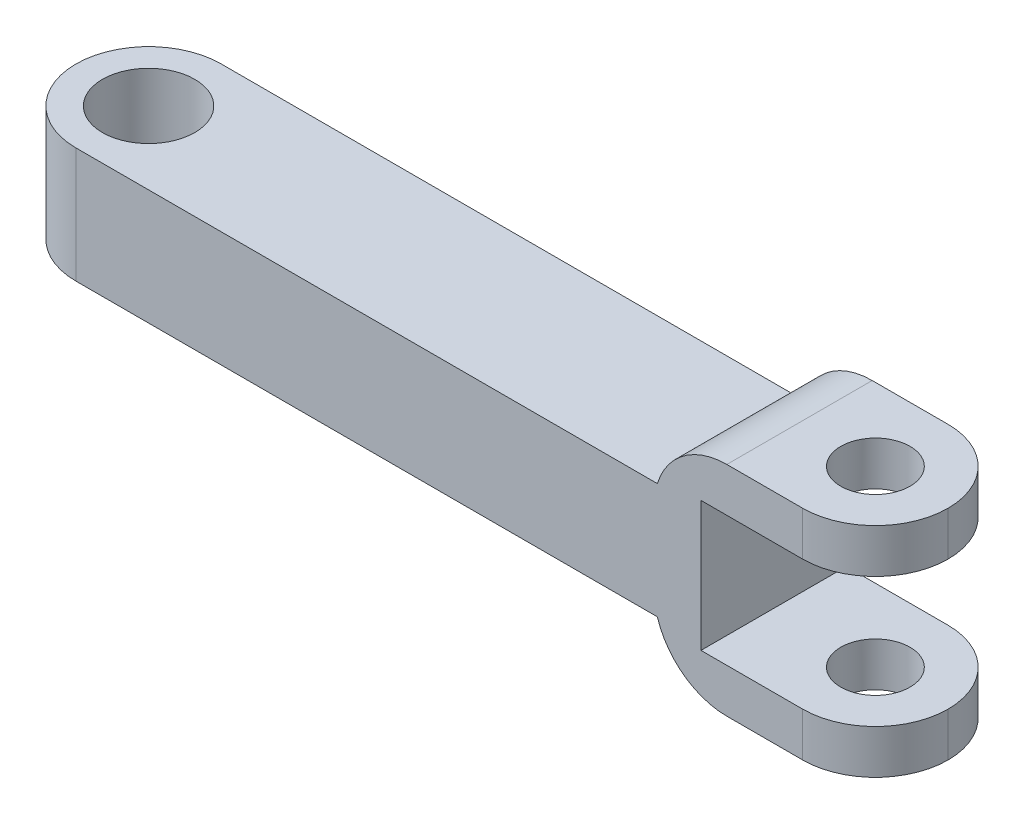
SolidWorks part; units mm, degrees
ref_plane "Front Plane" through (0, 0, 0) normal (0, 0, 1) x (1, 0, 0)
ref_plane "Top Plane" through (0, 0, 0) normal (0, 1, 0) x (1, 0, 0)
ref_plane "Right Plane" through (0, 0, 0) normal (1, 0, 0) x (0, 0, -1)
sketch "Sketch1" plane through (0, 0, 0) normal (0, 0, 1) x (1, 0, 0)
  line L1 (0, 0) -> (60, 0)
  line L2 (0, 0) -> (0, 15)
  line L3 (0, 15) -> (60, 15)
  line L4 (60, 0) -> (60, 15)
  dimension "D1" = 60
  dimension "D2" = 15
extrude "Boss-Extrude1" add sketch "Sketch1" along normal blind 10 contours L3 L4 L1 L2
sketch "Sketch2" plane through (0, 0, 10) normal (0, 0, 1) x (1, 0, 0)
  line L0 (0, 0) -> (0, 15) construction
  line L1 (0, 6.5) -> (10, 6.5) construction
  line L2 (0, 6.5) -> (0, 8.5) construction
  line L3 (0, 8.5) -> (10, 8.5) construction
  line L4 (10, 6.5) -> (10, 8.5) construction
  line L5 (60, 0) -> (60, 15) construction
  line L6 (60, 3.0313) -> (48, 3.0312)
  line L7 (60, 3.0313) -> (60, 11.9687)
  line L8 (60, 11.9687) -> (48, 11.9688)
  line L9 (48, 3.0312) -> (48, 11.9688)
  line L10 (0, 7.5) -> (60, 7.5)
  dimension "D1" = 2
  dimension "D2" = 8.9375
  dimension "D3" = 12
  dimension "D4" = 10
extrude "Cut-Extrude1" cut sketch "Sketch2" against normal through all contours L7 L6 L9 L8
sketch "Sketch4" plane through (0, 0, 10) normal (0, 0, 1) x (1, 0, 0)
  line L0 (0, 15) -> (60, 15) construction
  line L1 (0, 15) -> (45, 15)
  line L2 (0, 15) -> (0, 11.4688)
  line L3 (0, 3.5312) -> (45, 3.5312)
  line L4 (45, 15) -> (45, 11.4688)
  line L5 (0, 0) -> (60, 0) construction
  line L6 (0, 0) -> (45, 0)
  line L7 (0, 0) -> (0, 3.5312)
  line L8 (0, 11.4688) -> (45, 11.4688)
  line L9 (45, 0) -> (45, 3.5312)
  line L10 (60, 0) -> (60, 3.0313) construction
  line L13 (60, 11.9687) -> (60, 15) construction
  line L16 (0, 0) -> (0, 15) construction
  line L17 (0, 0) -> (0, 15) construction
  dimension "D1" = 7.9375
  dimension "D3" = 15
  dimension "D4" = 15
extrude "Cut-Extrude3" cut sketch "Sketch4" against normal through all
fillet "Fillet1" radius 5 6 edges at (60, 1.5156, 0) (60, 1.5156, 10) (60, 13.4844, 0) (60, 13.4844, 10) (0, 7.5, 0) (0, 7.5, 10)
fillet "Fillet2" radius 5 2 edges at (45, 0, 5) (45, 15, 5)
sketch "Sketch3" plane through (0, 15, 0) normal (0, 1, 0) x (1, 0, 0)
  circle A0 centre (5, -5) radius 3.175
  circle A1 centre (55, -5) radius 2.3813
  arc A2 (5, 0) -> (0, -5) centre (5, -5) ccw construction
  arc A3 (60, -5) -> (55, 0) centre (55, -5) ccw construction
  dimension "D2" = 4.7625
  dimension "D1" = 6.35
extrude "Cut-Extrude2" cut sketch "Sketch3" against normal through all
ref_axis "beam_hole_axis" through (55, 11.9688, 5) along (0, 1, 0)
ref_axis "crank_hole_axis" through (5, 3.5312, 5) along (0, 1, 0)
equation "\"coupler_length\"= 60"
equation "\"D1@Sketch1\"=\"coupler_length\""
equation "\"bearing_slot_diameter\"= 1in / 4"
equation "\"D1@Sketch3\"=\"bearing_slot_diameter\""
equation "\"pin_hole_diameter\"= 3in / 16"
equation "\"D2@Sketch3\"=\"pin_hole_diameter\""
